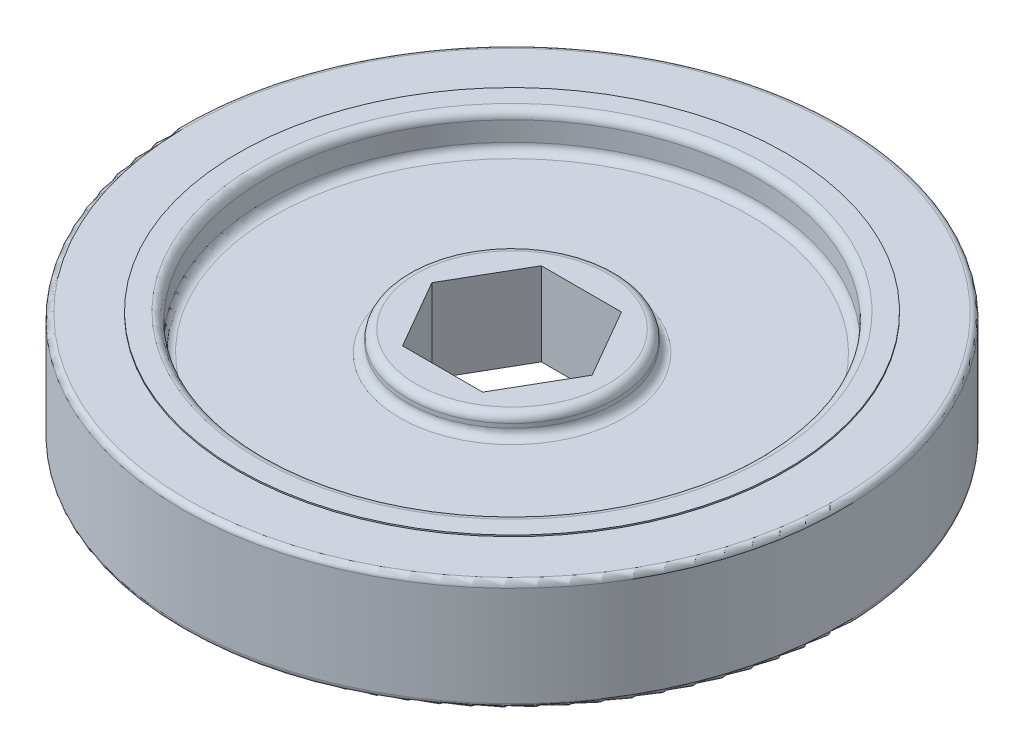
SolidWorks part; units mm, degrees
ref_plane "Front Plane" through (0, 0, 0) normal (0, 0, 1) x (1, 0, 0)
ref_plane "Top Plane" through (0, 0, 0) normal (0, 1, 0) x (1, 0, 0)
ref_plane "Right Plane" through (0, 0, 0) normal (1, 0, 0) x (0, 0, -1)
sketch "Sketch1" plane through (0, 0, 0) normal (0, 1, 0) x (1, 0, 0)
  line L1 (3.6662, 6.35) -> (-3.6662, 6.35)
  line L2 (-3.6662, 6.35) -> (-7.3323, 0)
  line L3 (-7.3323, 0) -> (-3.6662, -6.35)
  line L4 (-3.6662, -6.35) -> (3.6662, -6.35)
  line L5 (3.6662, -6.35) -> (7.3323, 0)
  line L6 (7.3323, 0) -> (3.6662, 6.35)
  circle A0 centre (0, 0) radius 30.1625
  circle A1 centre (0, 0) radius 6.35 construction
  circle A2 centre (0, 0) radius 25.0825
  circle A3 centre (0, 0) radius 22.5425
  circle A4 centre (0, 0) radius 9.525
  dimension "D1" = 60.325
  dimension "D3" = 5.08
  dimension "D4" = 2.54
  dimension "D5" = 19.05
  dimension "D2" = 12.7
extrude "Boss-Extrude1" add sketch "Sketch1" along normal mid plane 10.16 contours A0 A2 region at (-29.3094, 0, 0)
extrude "Boss-Extrude2" add sketch "Sketch1<3>" along normal mid plane 10.414 contours A2 A3 region at (-24.3731, 0, 0)
sketch "Sketch1<3>" plane through (0, 0, 0) normal (0, 1, 0) x (1, 0, 0) same geometry as "Sketch1"
extrude "Boss-Extrude3" add sketch "Sketch1<4>" along normal mid plane 7.62 separate body contours A4 L6 L5 L4 L3 L2 L1 region at (-9.2556, 0, 0)
sketch "Sketch1<4>" plane through (0, 0, 0) normal (0, 1, 0) x (1, 0, 0) same geometry as "Sketch1"
extrude "Boss-Extrude4" add sketch "Sketch1<5>" along normal mid plane 3.81 contours A3 A4 region at (-21.9049, 0, 0)
sketch "Sketch1<5>" plane through (0, 0, 0) normal (0, 1, 0) x (1, 0, 0) same geometry as "Sketch1"
fillet "Fillet1" radius 0.762 8 edges at (0, -1.905, 22.5425) (0, 5.207, 22.5425) (0, 1.905, 22.5425) (0, 3.81, 9.525) (0, 1.905, 9.525) (0, -5.207, 22.5425) (0, -3.81, 9.525) (0, -1.905, 9.525)
fillet "Fillet2" radius 0.508 2 edges at (0, -5.08, 30.1625) (0, 5.08, 30.1625)
